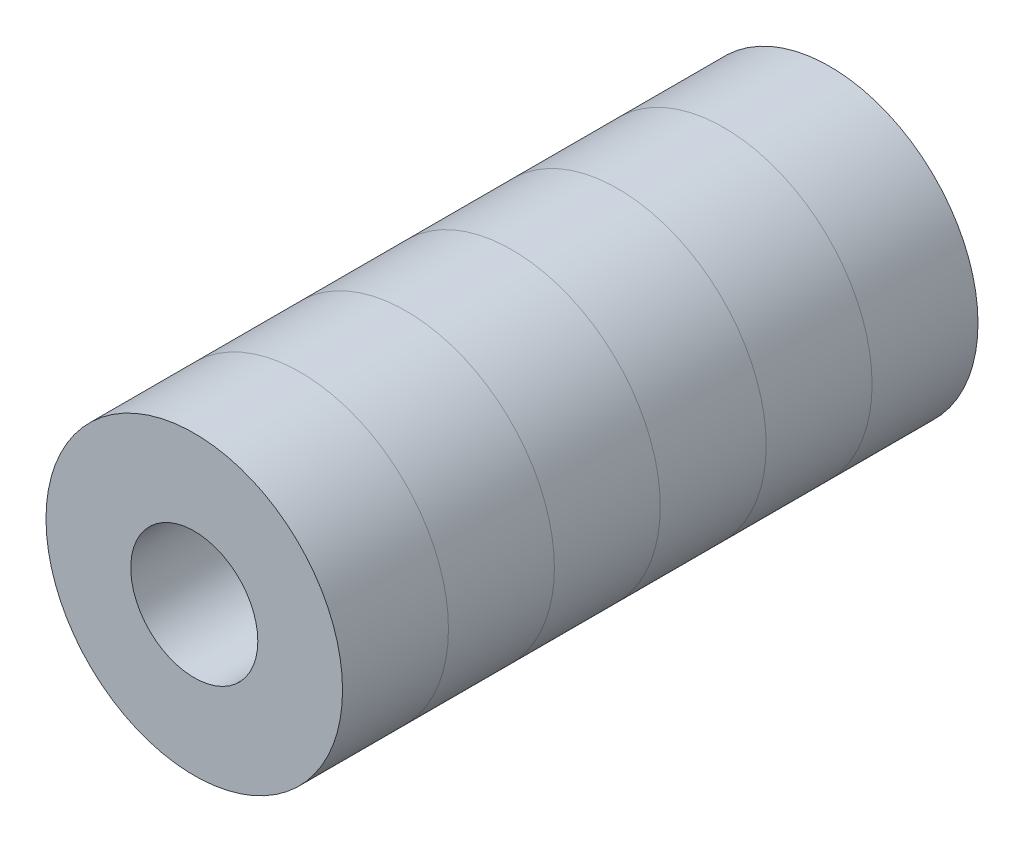
SolidWorks part; units mm, degrees
ref_plane "前视基准面" through (0, 0, 0) normal (0, 0, 1) x (1, 0, 0)
ref_plane "上视基准面" through (0, 0, 0) normal (0, 1, 0) x (1, 0, 0)
ref_plane "右视基准面" through (0, 0, 0) normal (1, 0, 0) x (0, 0, -1)
other "Configuration Table"
sketch "草图1" plane through (0, 0, 0) normal (0, 0, 1) x (1, 0, 0)
  circle A0 centre (0, 0) radius 3.5
  circle A1 centre (0, 0) radius 1.5
  dimension "D1" = 3
  dimension "D2" = 7
extrude "凸台-拉伸1" add sketch "草图1" along normal blind 2.5
pattern_linear "阵列(线性)1" count 6 spacing 2.5 along (0, 0, -1) of bodies 106
